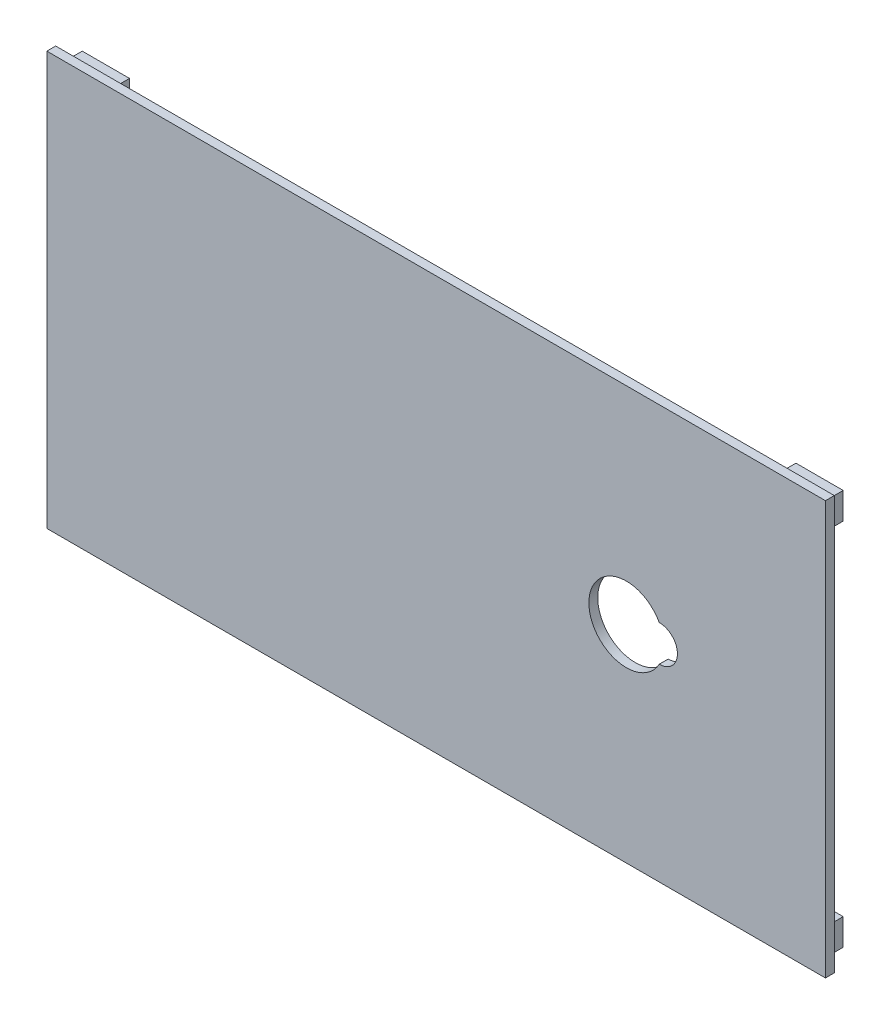
SolidWorks part; units mm, degrees
ref_plane "Front Plane" through (0, 0, 0) normal (0, 0, 1) x (1, 0, 0)
ref_plane "Top Plane" through (0, 0, 0) normal (0, 1, 0) x (1, 0, 0)
ref_plane "Right Plane" through (0, 0, 0) normal (1, 0, 0) x (0, 0, -1)
sketch "Sketch1" plane through (0, 0, 0) normal (0, 0, 1) x (1, 0, 0)
  line L0 (121.1, -9.75) -> (-10.75, -9.75)
  line L1 (119.6, -8.25) -> (-9.25, -8.25)
  line L2 (119.6, -8.25) -> (119.6, 58.75)
  line L3 (119.6, 58.75) -> (-9.25, 58.75)
  line L4 (-9.25, -8.25) -> (-9.25, 58.75)
  line L5 (-10.75, -9.75) -> (-10.75, 60.25)
  line L6 (121.1, 60.25) -> (-10.75, 60.25)
  line L7 (121.1, -9.75) -> (121.1, 60.25)
  dimension "D1" = 1.5
extrude "Boss-Extrude1" add sketch "Sketch1" along normal blind 1.5 contours L7 L6 L5 L0
sketch "Sketch2" plane through (0, 0, 1.5) normal (0, 0, 1) x (1, 0, 0)
  line L5 (92.9571, 22.2) -> (92.9875, 22.2)
  line L6 (92.9875, 28.3) -> (92.9571, 28.3)
  line L7 (92.9571, 22.2) -> (92.9875, 22.2)
  line L8 (92.9875, 28.3) -> (92.9571, 28.3)
  arc A10 (92.9875, 22.2) -> (92.9875, 28.3) centre (92.9875, 25.25) ccw
  arc A11 (92.9571, 28.3) -> (92.9571, 22.2) centre (87.3875, 25.25) ccw
  arc A12 (92.9875, 22.2) -> (92.9875, 28.3) centre (92.9875, 25.25) ccw
  arc A13 (92.9571, 28.3) -> (92.9571, 22.2) centre (87.3875, 25.25) ccw
  dimension "D1" = 0.25
extrude "Cut-Extrude1" cut sketch "Sketch2" against normal up to next
ref_plane "Plane2" through (0, 25.25, 0) normal (0, 1, 0) x (1, 0, 0)
ref_plane "Plane1" through (55.175, 0, 0) normal (1, 0, 0) x (0, 0, -1)
sketch "Sketch3" plane through (121.1, 0, 0) normal (1, 0, 0) x (0, 0, -1)
  line L0 (0, -9.75) -> (0, 60.25) construction
  line L1 (-1.5, 60.25) -> (6, 60.25)
  line L2 (-1.5, 60.25) -> (-1.5, 61.75)
  line L3 (-1.5, 61.75) -> (6, 61.75)
  line L4 (6, 60.25) -> (6, 61.75)
  line L5 (6, 60.25) -> (4.5, 58.75)
  line L7 (4.5, 58.75) -> (4.5, 60.25)
  dimension "D1" = 1.5
  dimension "D2" = 6
  dimension "D3" = 45
sketch "Sketch4" plane through (0, 0, 0) normal (0, 0, -1) x (-1, 0, 0)
  line L0 (-118.1, 57.25) -> (-118.1, 55.75)
  line L1 (-119.6, 58.75) -> (-111.6, 58.75)
  line L2 (-119.6, 58.75) -> (-119.6, 54.25)
  line L3 (-119.6, 54.25) -> (-111.6, 54.25)
  line L4 (-111.6, 58.75) -> (-111.6, 54.25)
  line L5 (-119.6, 58.75) -> (-119.6, 60.25) construction
  line L6 (-118.1, 55.75) -> (-113.1, 55.75)
  line L7 (-121.1, 60.25) -> (10.75, 60.25) construction
  line L8 (-113.1, 57.25) -> (-113.1, 55.75)
  line L9 (-118.1, 57.25) -> (-113.1, 57.25)
  line L10 (-119.6, 58.75) -> (-121.1, 58.75) construction
  line L11 (-121.1, -9.75) -> (-121.1, 60.25) construction
  dimension "D1" = 1.5
  dimension "D2" = 5
  dimension "D3" = 1.5
extrude "Boss-Extrude2" add sketch "Sketch4" along normal blind 3
mirror "Mirror1" about plane through (0, 25.25, 0) normal (0, 1, 0) of "Boss-Extrude2"
mirror "Mirror2" about plane through (55.175, 0, 0) normal (1, 0, 0) of "Mirror1", "Boss-Extrude2"
equation "\"D1@Boss-Extrude2\"=1.50mm+.25"
